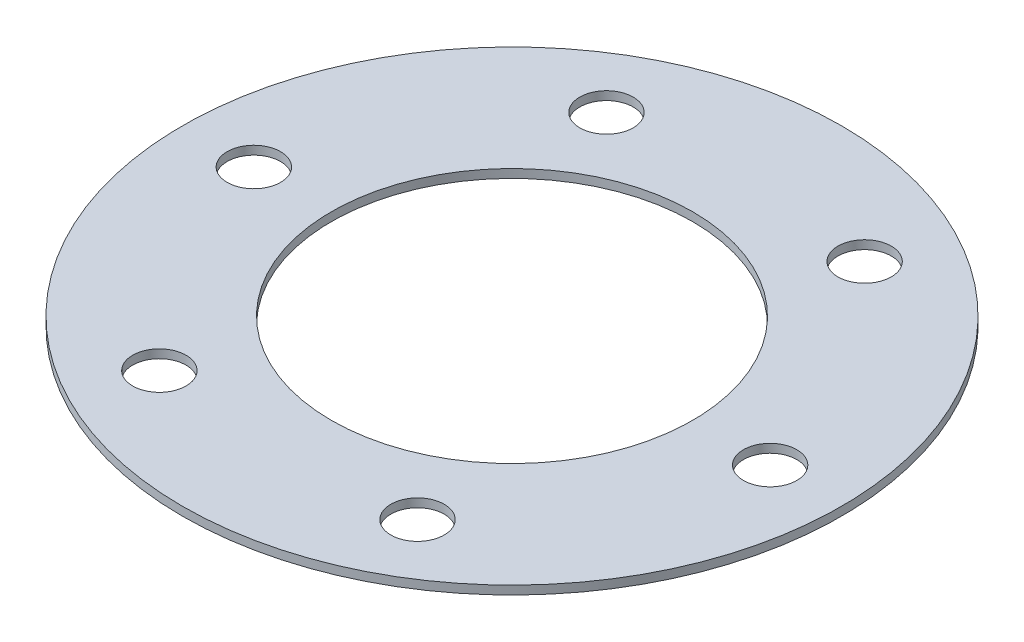
SolidWorks part; units mm, degrees
material "Balsa"
ref_plane "Front Plane" through (0, 0, 0) normal (0, 0, 1) x (1, 0, 0)
ref_plane "Top Plane" through (0, 0, 0) normal (0, 1, 0) x (1, 0, 0)
ref_plane "Right Plane" through (0, 0, 0) normal (1, 0, 0) x (0, 0, -1)
sketch "Sketch1" plane through (0, 0, 0) normal (0, 1, 0) x (1, 0, 0)
  line L0 (-38.3, 0) -> (38.3, 0) construction
  line L1 (0, 38.3) -> (0, -38.3) construction
  circle A0 centre (0, 0) radius 38.3
  circle A1 centre (30, 0) radius 3.1
  circle A2 centre (0, 0) radius 21
  circle A3 centre (15, -25.9808) radius 3.1
  circle A4 centre (-15, -25.9808) radius 3.1
  circle A5 centre (-30, 0) radius 3.1
  circle A6 centre (-15, 25.9808) radius 3.1
  circle A7 centre (15, 25.9808) radius 3.1
  point P23 (0, 0)
  dimension "D1" = 42
  dimension "D2" = 76.6
  dimension "D3" = 6.2
  dimension "D4" = 30
  dimension "D5" = 6
extrude "Boss-Extrude1" add sketch "Sketch1" along normal blind 1
